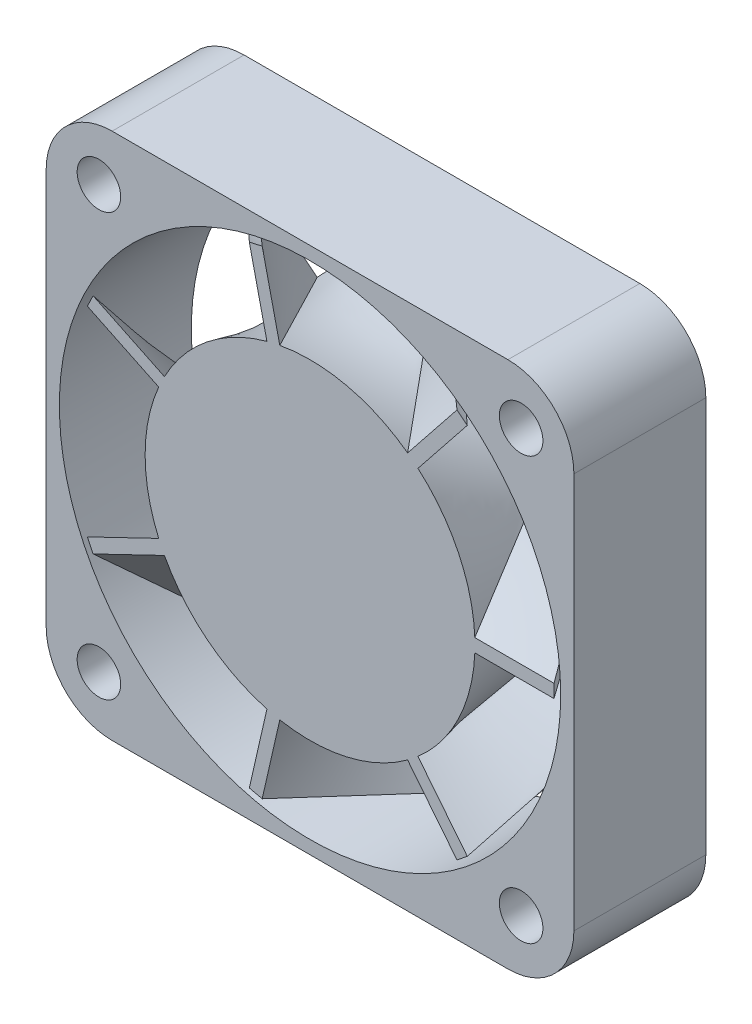
SolidWorks part; units mm, degrees
ref_plane "Front Plane" through (0, 0, 0) normal (0, 0, 1) x (1, 0, 0)
ref_plane "Top Plane" through (0, 0, 0) normal (0, 1, 0) x (1, 0, 0)
ref_plane "Right Plane" through (0, 0, 0) normal (1, 0, 0) x (0, 0, -1)
sketch "Sketch1" plane through (0, 0, 0) normal (0, 0, 1) x (1, 0, 0)
  line L0 (40, 20) -> (20, 20) construction
  line L1 (0, 0) -> (40, 0)
  line L2 (0, 0) -> (0, 40)
  line L3 (0, 40) -> (40, 40)
  line L4 (40, 0) -> (40, 40)
  line L5 (20, 20) -> (20, 0) construction
  circle A0 centre (20, 20) radius 19
  circle A1 centre (4, 4) radius 1.65
  circle A2 centre (36, 4) radius 1.65
  circle A3 centre (36, 36) radius 1.65
  circle A4 centre (4, 36) radius 1.65
  dimension "D3" = 38
  dimension "D4" = 3.3
  dimension "D7" = 32
  dimension "D8" = 32
  dimension "D1" = 40
  dimension "D2" = 40
  dimension "D9" = 4
  dimension "D10" = 4
  dimension "D5" = 2
  dimension "D6" = 2
extrude "Boss-Extrude1" add sketch "Sketch1" along normal blind 10
fillet "Fillet1" radius 5 4 edges at (40, 0, 5) (0, 0, 5) (0, 40, 5) (40, 40, 5)
sketch "Sketch3" plane through (0, 0, 0) normal (0, 0, 1) x (1, 0, 0)
  line L0 (19.5, 32.49) -> (19.5, 38.49)
  line L1 (19.5, 38.49) -> (20.5, 38.49)
  line L2 (20.5, 38.49) -> (20.5, 32.49)
  line L3 (29.4533, 28.1783) -> (34.1443, 31.9192)
  line L4 (34.1443, 31.9192) -> (34.7678, 31.1374)
  line L5 (34.7678, 31.1374) -> (30.0768, 27.3965)
  line L6 (32.2881, 17.7082) -> (38.1377, 16.3731)
  line L7 (38.1377, 16.3731) -> (37.9152, 15.3981)
  line L8 (37.9152, 15.3981) -> (32.0656, 16.7333)
  line L9 (25.8697, 8.9638) -> (28.473, 3.558)
  line L10 (28.473, 3.558) -> (27.572, 3.1241)
  line L11 (27.572, 3.1241) -> (24.9687, 8.53)
  line L12 (15.0313, 8.53) -> (12.428, 3.1241)
  line L13 (12.428, 3.1241) -> (11.527, 3.558)
  line L14 (11.527, 3.558) -> (14.1303, 8.9638)
  line L15 (7.9344, 16.7333) -> (2.0848, 15.3981)
  line L16 (2.0848, 15.3981) -> (1.8623, 16.3731)
  line L17 (1.8623, 16.3731) -> (7.7119, 17.7082)
  line L18 (9.9232, 27.3965) -> (5.2322, 31.1374)
  line L19 (5.2322, 31.1374) -> (5.8557, 31.9192)
  line L20 (5.8557, 31.9192) -> (10.5467, 28.1783)
  arc A0 (19.5, 32.49) -> (10.5467, 28.1783) centre (20, 20) ccw
  circle A1 centre (20, 20) radius 19 construction
  arc A2 (29.4533, 28.1783) -> (20.5, 32.49) centre (20, 20) ccw
  arc A3 (32.2881, 17.7082) -> (30.0768, 27.3965) centre (20, 20) ccw
  arc A4 (25.8697, 8.9638) -> (32.0656, 16.7333) centre (20, 20) ccw
  arc A5 (15.0313, 8.53) -> (24.9687, 8.53) centre (20, 20) ccw
  arc A6 (7.9344, 16.7333) -> (14.1303, 8.9638) centre (20, 20) ccw
  arc A7 (9.9232, 27.3965) -> (7.7119, 17.7082) centre (20, 20) ccw
  point P33 (20, 20)
  dimension "D1" = 25
  dimension "D2" = 1
  dimension "D3" = 6
  dimension "D4" = 7
sketch "Sketch5" plane through (0, 0, 10) normal (0, 0, 1) x (1, 0, 0)
  line L0 (32.49, 20.5) -> (38.49, 20.5)
  line L1 (38.49, 20.5) -> (38.49, 19.5)
  line L2 (38.49, 19.5) -> (32.49, 19.5)
  line L3 (28.1783, 10.5467) -> (31.9192, 5.8557)
  line L4 (31.9192, 5.8557) -> (31.1374, 5.2322)
  line L5 (31.1374, 5.2322) -> (27.3965, 9.9232)
  line L6 (17.7082, 7.7119) -> (16.3731, 1.8623)
  line L7 (16.3731, 1.8623) -> (15.3981, 2.0848)
  line L8 (15.3981, 2.0848) -> (16.7333, 7.9344)
  line L9 (8.9638, 14.1303) -> (3.558, 11.527)
  line L10 (3.558, 11.527) -> (3.1241, 12.428)
  line L11 (3.1241, 12.428) -> (8.53, 15.0313)
  line L12 (8.53, 24.9687) -> (3.1241, 27.572)
  line L13 (3.1241, 27.572) -> (3.558, 28.473)
  line L14 (3.558, 28.473) -> (8.9638, 25.8697)
  line L15 (16.7333, 32.0656) -> (15.3981, 37.9152)
  line L16 (15.3981, 37.9152) -> (16.3731, 38.1377)
  line L17 (16.3731, 38.1377) -> (17.7082, 32.2881)
  line L18 (27.3965, 30.0768) -> (31.1374, 34.7678)
  line L19 (31.1374, 34.7678) -> (31.9192, 34.1443)
  line L20 (31.9192, 34.1443) -> (28.1783, 29.4533)
  arc A0 (32.49, 20.5) -> (28.1783, 29.4533) centre (20, 20) ccw
  arc A1 (27.3965, 30.0768) -> (17.7082, 32.2881) centre (20, 20) ccw
  arc A2 (16.7333, 32.0656) -> (8.9638, 25.8697) centre (20, 20) ccw
  arc A3 (8.53, 24.9687) -> (8.53, 15.0313) centre (20, 20) ccw
  arc A4 (8.9638, 14.1303) -> (16.7333, 7.9344) centre (20, 20) ccw
  arc A5 (17.7082, 7.7119) -> (27.3965, 9.9232) centre (20, 20) ccw
  arc A6 (28.1783, 10.5467) -> (32.49, 19.5) centre (20, 20) ccw
  point P33 (20, 20)
  dimension "D1" = 1
  dimension "D2" = 6
  dimension "D3" = 7
loft "Loft1" add profiles "Sketch3", "Sketch5" connector at (10.5467, 28.1783, 0) connector at (17.7082, 32.2881, 10)
